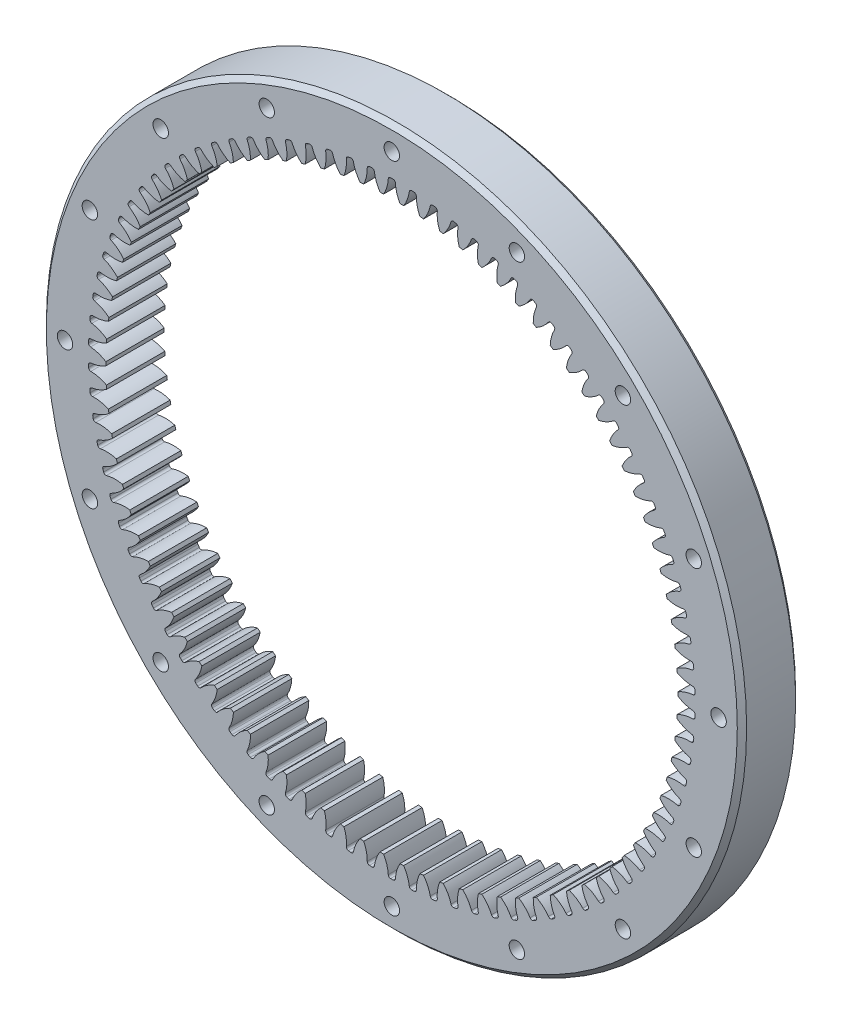
SolidWorks part; units mm, degrees
ref_plane "Front Plane" through (0, 0, 0) normal (0, 0, 1) x (1, 0, 0)
ref_plane "Top Plane" through (0, 0, 0) normal (0, 1, 0) x (1, 0, 0)
ref_plane "Right Plane" through (0, 0, 0) normal (1, 0, 0) x (0, 0, -1)
sketch "Sketch1" plane through (0, 0, 0) normal (0, 0, 1) x (1, 0, 0)
  circle A0 centre (0, 0) radius 150
  circle A1 centre (0, 0) radius 122.5
  dimension "D1" = 300
  dimension "D2" = 245
extrude "Boss-Extrude1" add sketch "Sketch1" along normal mid plane 25
ref_axis "Axis1" through (0, 0, 12.5) along (0, 0, -1)
sketch "Sketch2" plane through (0, 0, 12.5) normal (0, 0, 1) x (1, 0, 0)
  line L0 (0, 0) -> (0, 130) construction
  circle A0 centre (0, 0) radius 125 construction
  circle A1 centre (0, 0) radius 130 construction
  arc A2 (-1.5, 129.9913) -> (-3.5, 122.45) centre (-16.4999, 129.9335) cw
  circle A3 centre (0, 0) radius 122.5 construction
  arc A4 (1.5, 129.9913) -> (3.5, 122.45) centre (16.4999, 129.9335) ccw
  arc A5 (-1.5, 129.9913) -> (1.5, 129.9913) centre (0, 0) cw
  circle A6 centre (0, 0) radius 122.5
  circle M8 centre (0, 0) radius 122.5
  dimension "D1" = 250
  dimension "D2" = 260
  dimension "D4" = 15
  dimension "D3" = 7
  dimension "D5" = 3
extrude "Cut-Extrude1" cut sketch "Sketch2" against normal through all contours A5 A2 A4 M8 region at (0, 125.6683, 12.5)
fillet "Fillet1" radius 1 2 edges at (1.5, 129.9913, 0) (-1.5, 129.9913, 0)
pattern_circular "CirPattern1" count 90 over 360 about axis through (0, 0, 12.5) along (0, 0, -1) of "Cut-Extrude1", "Fillet1"
chamfer "Chamfer1" distance 2 angle 45 2 edges at (150, 0, -12.5) (150, 0, 12.5)
sketch "Sketch5" plane through (0, 0, 12.5) normal (0, 0, 1) x (1, 0, 0)
  circle A0 centre (0, 0) radius 140 construction
  circle A1 centre (0, 140) radius 3.3
  dimension "D1" = 280
  dimension "D2" = 6.6
extrude "Cut-Extrude2" cut sketch "Sketch5" against normal through all
pattern_circular "CirPattern2" count 16 over 360 about axis through (0, 0, 12.5) along (0, 0, -1) of "Cut-Extrude2"
